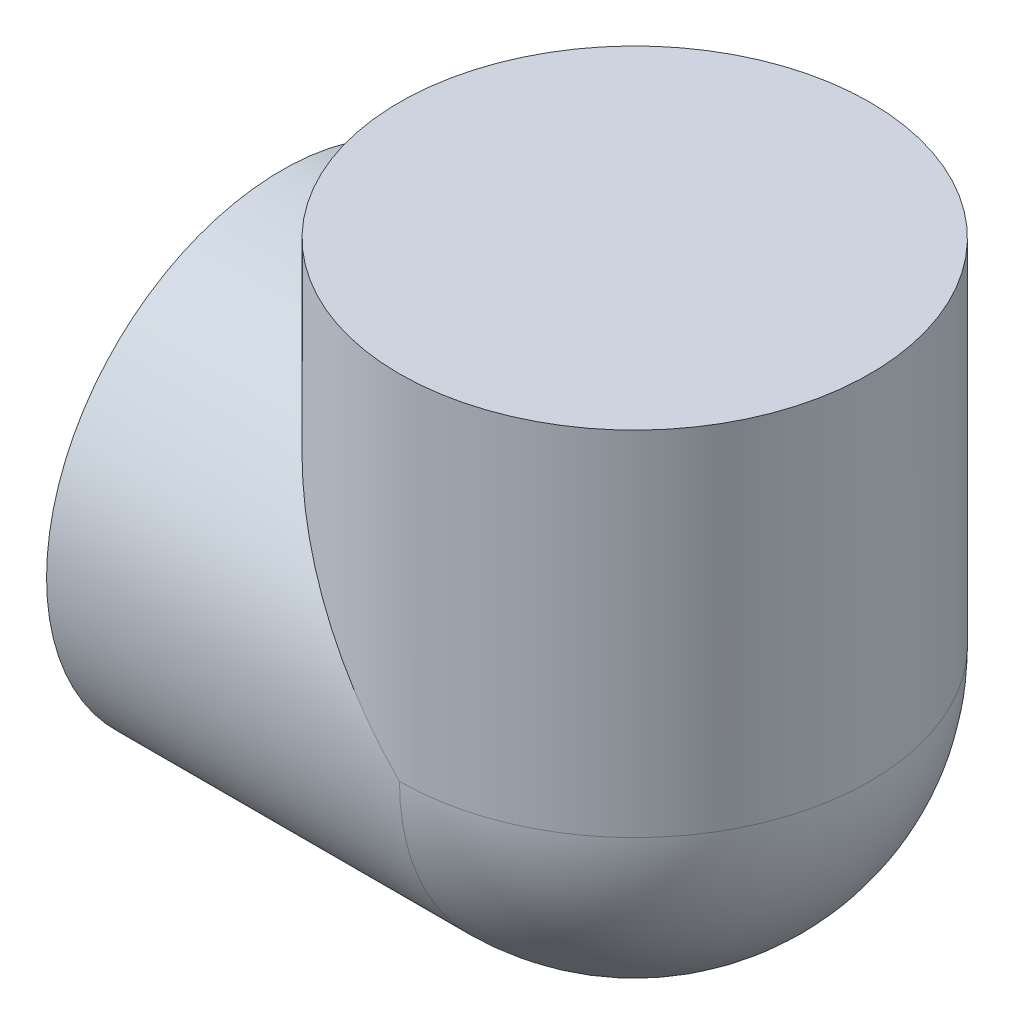
SolidWorks part; units mm, degrees
ref_plane "Front Plane" through (0, 0, 0) normal (0, 0, 1) x (1, 0, 0)
ref_plane "Top Plane" through (0, 0, 0) normal (0, 1, 0) x (1, 0, 0)
ref_plane "Right Plane" through (0, 0, 0) normal (1, 0, 0) x (0, 0, -1)
sketch "Sketch1" plane through (30, 0, 0) normal (1, 0, 0) x (0, 0, -1)
  line L0 (20, 80) -> (-20, 80)
  arc A0 (-20, 80) -> (20, 80) centre (0, 80) ccw
extrude "Boss-Extrude1" add sketch "Sketch1" along normal blind 50
fillet "Fillet1" radius 20 1 edges at (80, 60, 0) conic radius 20
sketch "Sketch2" plane through (0, 80, 0) normal (0, 1, 0) x (1, 0, 0)
  circle A0 centre (60, 0) radius 20
extrude "Boss-Extrude2" add sketch "Sketch2" along normal blind 30
sketch "Sketch3" plane through (30, 0, 0) normal (1, 0, 0) x (0, 0, -1)
  line L0 (20, 80) -> (-20, 80) construction
  line L1 (-20, 80) -> (20, 80)
  arc A0 (20, 80) -> (-20, 80) centre (0, 80) ccw
extrude "Boss-Extrude3" add sketch "Sketch3" along normal blind 30
